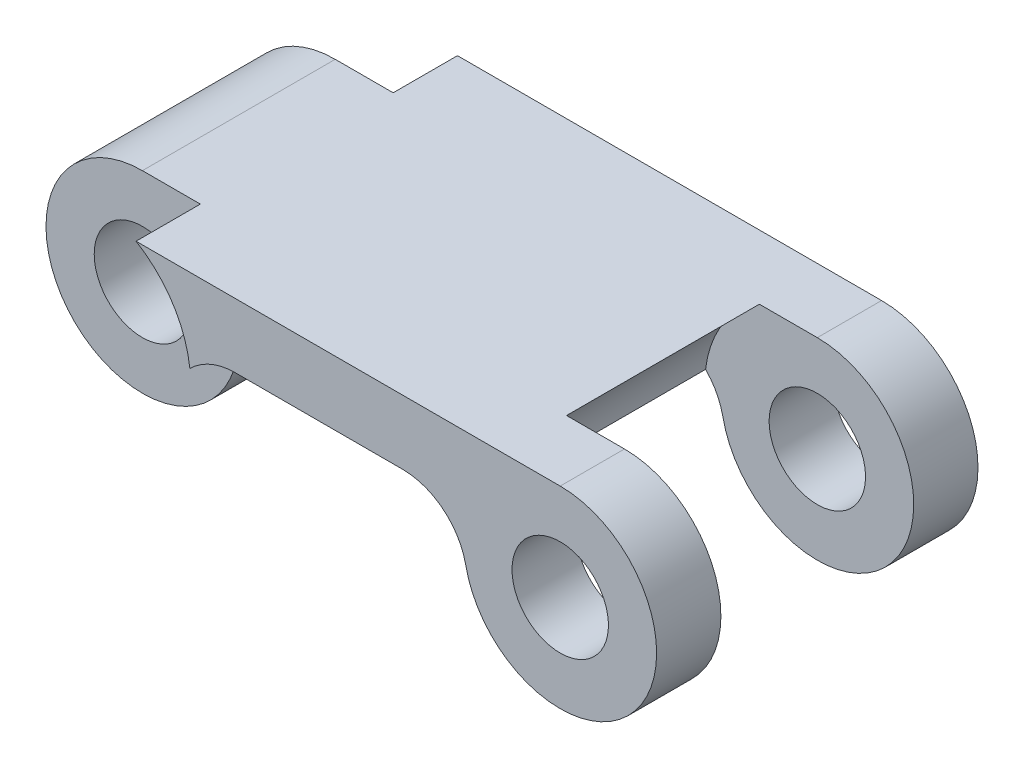
SolidWorks part; units mm, degrees
ref_plane "Piano frontale" through (0, 0, 0) normal (0, 0, 1) x (1, 0, 0)
ref_plane "Piano superiore" through (0, 0, 0) normal (0, 1, 0) x (1, 0, 0)
ref_plane "Piano destro" through (0, 0, 0) normal (1, 0, 0) x (0, 0, -1)
sketch "Schizzo1" plane through (0, 0, 0) normal (0, 0, 1) x (1, 0, 0)
  line L0 (-24.825, 11.3137) -> (-9.825, 11.3137)
  line L1 (-21.9965, 9.3137) -> (-12.6534, 9.3137)
  arc A0 (-24.825, 11.3137) -> (-21.9965, 9.3137) centre (-24.825, 8.3137) ccw
  arc A1 (-9.825, 11.3137) -> (-12.6534, 9.3137) centre (-9.825, 8.3137) cw
  dimension "D1" = 3
  dimension "D2" = 3
  dimension "D3" = 2
  dimension "D5" = 15
extrude "Estrusione-Estrusione1" add sketch "Schizzo1" along normal blind 10
sketch "Schizzo5" plane through (0, 0, 0) normal (0, 0, -1) x (-1, 0, 0)
  circle A0 centre (9.825, 8.3137) radius 1.5
  circle A1 centre (24.825, 8.3137) radius 1.5
  arc A2 (21.9965, 9.3137) -> (24.825, 11.3137) centre (24.825, 8.3137) ccw construction
  arc A3 (9.825, 11.3137) -> (12.6534, 9.3137) centre (9.825, 8.3137) ccw construction
  dimension "D1" = 0
  dimension "D3" = 3
  dimension "D4" = 3
  dimension "D2" = 0
extrude "Taglio-Estrusione1" cut sketch "Schizzo5" against normal blind 10
sketch "Schizzo6" plane through (0, 0, 0) normal (0, 0, -1) x (-1, 0, 0)
  circle A0 centre (24.825, 8.3137) radius 3.5
  dimension "D1" = 7
extrude "Taglio-Estrusione2" cut sketch "Schizzo6" against normal blind 2
extrude "Taglio-Estrusione3" cut sketch "Schizzo6<2>" against normal blind 12 from offset 8 offset against normal yes
sketch "Schizzo6<2>" plane through (0, 0, 0) normal (0, 0, -1) x (-1, 0, 0) same geometry as "Schizzo6"
sketch "Schizzo7" plane through (0, 0, 0) normal (0, 0, -1) x (-1, 0, 0)
  circle A0 centre (9.825, 8.3137) radius 3.5
  dimension "D1" = 7
extrude "Taglio-Estrusione4" cut sketch "Schizzo7" against normal blind 6 from offset 2 offset against normal yes
fillet "Raccordo1" radius 2 1 edges at (-21.9965, 9.3137, 5)
fillet "Raccordo2" radius 2 1 edges at (-12.6534, 9.3137, 1)
